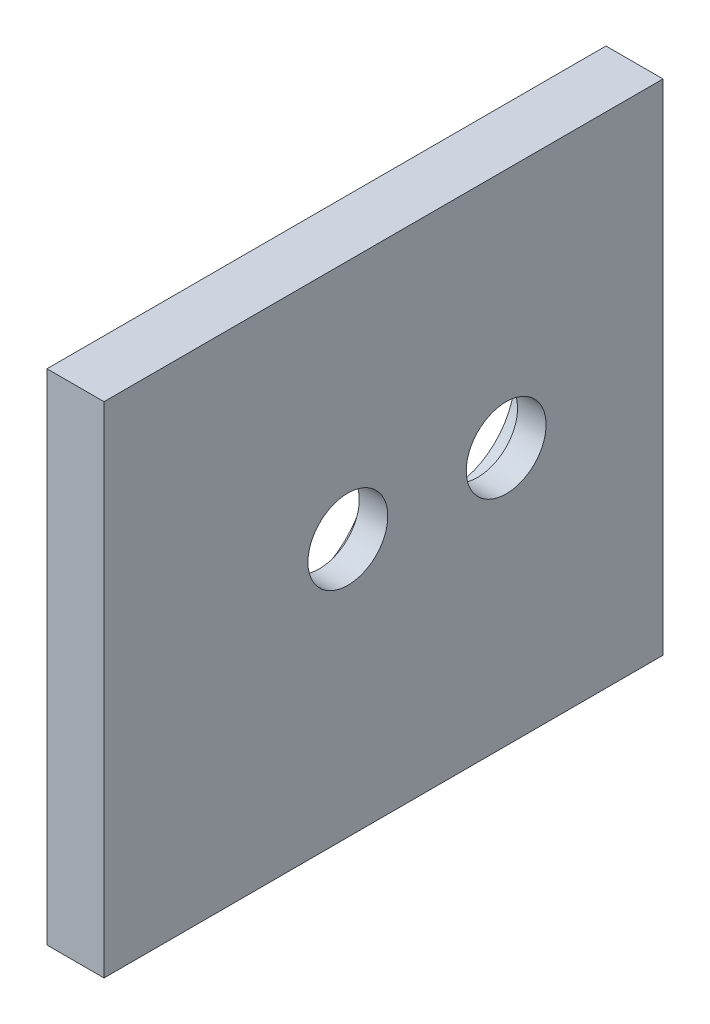
SolidWorks part; units mm, degrees
ref_plane "Front Plane" through (0, 0, 0) normal (0, 0, 1) x (1, 0, 0)
ref_plane "Top Plane" through (0, 0, 0) normal (0, 1, 0) x (1, 0, 0)
ref_plane "Right Plane" through (0, 0, 0) normal (1, 0, 0) x (0, 0, -1)
sketch "Sketch1" plane through (114, 0, 0) normal (0, 1, 0) x (1, 0, 0)
  line L0 (-104, 0) -> (-114, 0) construction
  line L1 (-124, 98) -> (-104, 98)
  line L2 (-124, 98) -> (-124, -98)
  line L3 (-124, -98) -> (-104, -98)
  line L4 (-104, 98) -> (-104, -98)
  line L5 (-114, -96.25) -> (-114, 96.25) construction
  point P9 (-114, -98)
  dimension "D1" = 20
  dimension "D2" = 196
extrude "Boss-Extrude1" add sketch "Sketch1" along normal blind 175
sketch "Sketch2" plane through (-10, 0, 0) normal (-1, 0, 0) x (0, 0, 1)
  line L2 (0, -11) -> (0, 11) construction
  line L3 (0, -96.25) -> (0, 96.25) construction
  line L4 (98, 175) -> (98, 0) construction
  line L5 (-98, 0) -> (98, 0) construction
  line L6 (-98, 175) -> (-98, 0) construction
  circle A1 centre (12.5, 90.5) radius 27.5
  circle A2 centre (-43, 90.5) radius 23
  point P4 (0, 0)
  dimension "D1" = 55
  dimension "D2" = 46
  dimension "D5" = 58
  dimension "D6" = 63
  dimension "D7" = 90.5
  dimension "D8" = 32
  dimension "D3" = 12.5
  dimension "D4" = 43
extrude "Cut-Extrude1" cut sketch "Sketch2" against normal blind 10
sketch "Sketch3" plane through (0, 0, 0) normal (-1, 0, 0) x (0, 0, 1)
  circle A0 centre (12.5, 90.5) radius 14
  circle A1 centre (-43, 90.5) radius 14
  circle A2 centre (-43, 90.5) radius 23 construction
  circle A3 centre (12.5, 90.5) radius 27.5 construction
  dimension "D1" = 28
extrude "Cut-Extrude2" cut sketch "Sketch3" against normal through all
